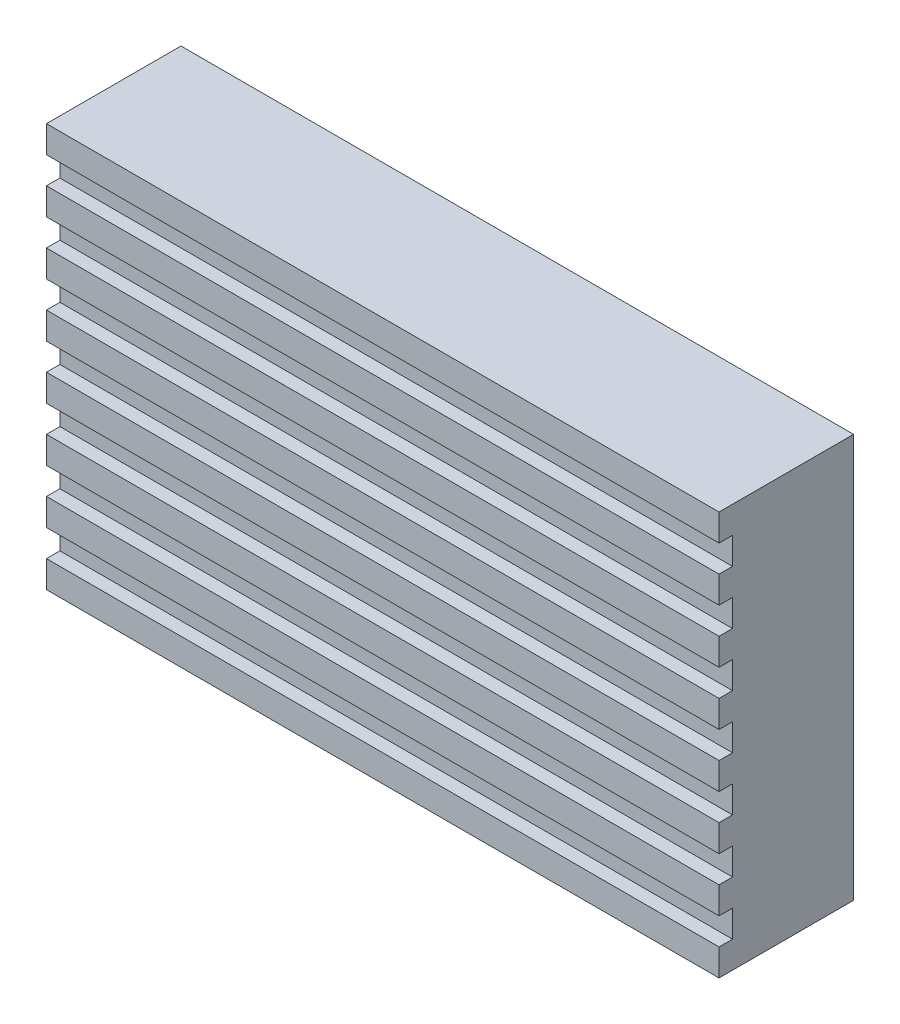
SolidWorks part; units mm, degrees
ref_plane "Front Plane" through (0, 0, 0) normal (0, 0, 1) x (1, 0, 0)
ref_plane "Top Plane" through (0, 0, 0) normal (0, 1, 0) x (1, 0, 0)
ref_plane "Right Plane" through (0, 0, 0) normal (1, 0, 0) x (0, 0, -1)
sketch "Sketch1" plane through (0, 0, 0) normal (0, 0, 1) x (1, 0, 0)
  line L1 (0, 0) -> (-50, 0)
  line L2 (0, 0) -> (0, -30)
  line L3 (0, -30) -> (-50, -30)
  line L4 (-50, 0) -> (-50, -30)
  dimension "D1" = 50
  dimension "D2" = 30
extrude "Boss-Extrude1" add sketch "Sketch1" along normal blind 10
sketch "Sketch2" plane through (0, 0, 10) normal (0, 0, 1) x (1, 0, 0)
  line L0 (-50, -2) -> (0, -2)
  line L1 (-50, 0) -> (-50, -30) construction
  line L2 (0, -30) -> (0, 0) construction
  line L3 (0, 0) -> (-50, 0) construction
  line L4 (-50, -4) -> (0, -4)
  line L5 (-50, -4) -> (-50, -2)
  line L6 (0, -2) -> (0, -4)
  line L7 (-50, -8) -> (0, -8)
  line L8 (-50, -8) -> (-50, -6)
  line L9 (-50, -6) -> (0, -6)
  line L10 (0, -6) -> (0, -8)
  line L11 (-50, -12) -> (0, -12)
  line L12 (-50, -12) -> (-50, -10)
  line L13 (-50, -10) -> (0, -10)
  line L14 (0, -10) -> (0, -12)
  line L15 (-50, -16) -> (0, -16)
  line L16 (-50, -16) -> (-50, -14)
  line L17 (-50, -14) -> (0, -14)
  line L18 (0, -14) -> (0, -16)
  line L19 (-50, -20) -> (0, -20)
  line L20 (-50, -20) -> (-50, -18)
  line L21 (-50, -18) -> (0, -18)
  line L22 (0, -18) -> (0, -20)
  line L23 (-50, -24) -> (0, -24)
  line L24 (-50, -24) -> (-50, -22)
  line L25 (-50, -22) -> (0, -22)
  line L26 (0, -22) -> (0, -24)
  line L27 (-50, -28) -> (0, -28)
  line L28 (-50, -28) -> (-50, -26)
  line L29 (-50, -26) -> (0, -26)
  line L30 (-50, -8) -> (0, -8) [skipped]
  line L31 (-50, -10) -> (0, -10) [skipped]
  line L32 (-50, -12) -> (0, -12) [skipped]
  line L33 (-50, -14) -> (0, -14) [skipped]
  line L34 (-50, -16) -> (0, -16) [skipped]
  line L35 (-50, -18) -> (0, -18) [skipped]
  line L36 (-50, -20) -> (0, -20) [skipped]
  line L37 (-50, -22) -> (0, -22) [skipped]
  line L38 (-50, -24) -> (0, -24) [skipped]
  line L39 (-50, -26) -> (0, -26) [skipped]
  line L40 (-50, -28) -> (0, -28) [skipped]
  line L41 (-50, -6) -> (0, -6) [skipped]
  line L42 (0, -26) -> (0, -28)
  dimension "D1" = 2
  dimension "D3" = 7
  dimension "D2" = 14
extrude "Cut-Extrude3" cut sketch "Sketch2" against normal blind 1
sketch "Sketch3" plane through (0, 0, 10) normal (0, 0, 1) x (1, 0, 0)
  line L0 (-50, 0) -> (-50, -30) construction
  line L1 (-50, -30) -> (-50, -15) construction
  line L2 (-50, -15) -> (7.6959, -15) construction
